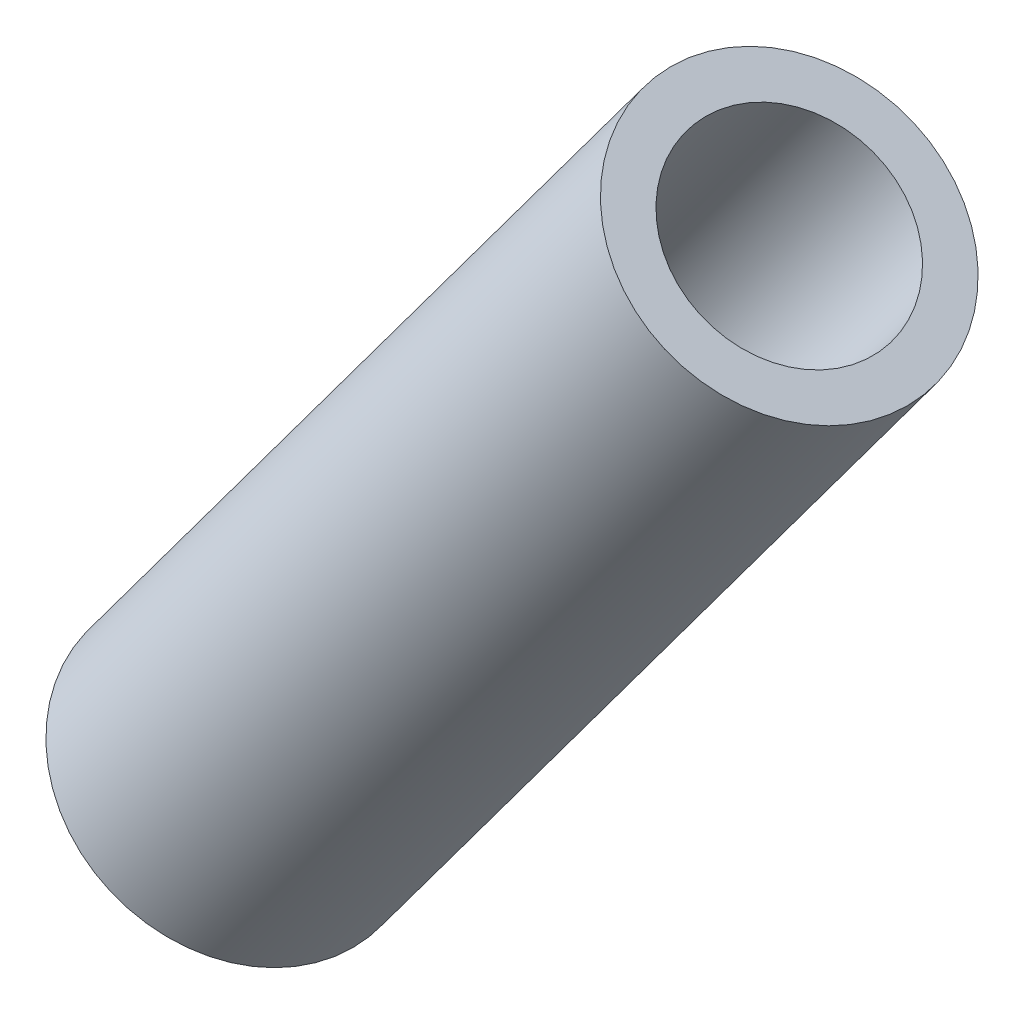
SolidWorks part; units mm, degrees
material "Silicon Rubber"
ref_plane "X-Y Datum" through (0, 0, 0) normal (0, 0, 1) x (1, 0, 0)
ref_plane "X-Z Datum" through (0, 0, 0) normal (0, 1, 0) x (1, 0, 0)
ref_plane "Y-Z Datum" through (0, 0, 0) normal (1, 0, 0) x (0, 0, -1)
sketch3d "3DSketch1"
  line L0 (-20.5114, -27.616, 0) -> (30.2901, 40.7817, 0)
  circle A0 centre (-20.5114, -27.616, 0) radius 10 construction
  circle A1 centre (-20.5114, -27.616, 0) radius 10 construction
  circle A2 centre (30.2901, 40.7817, 0) radius 9.5 construction
  circle A3 centre (30.2901, 40.7817, 0) radius 9.5 construction
  point P5 (-14.5488, -19.5881, 0)
  point P7 (-14.5488, -19.5881, 0)
  point P8 (0, 0, 0)
  point P11 (35.9546, 48.4082, 0)
  point P12 (35.9546, 48.4082, 0)
  point P13 (0, 0, 0)
  point P14 (0, 0, 0)
sweep "Sweep1" add path "3DSketch1" circular profile diameter 26.9875 parameters "D3"=26.9875
sweep "Cut-Sweep1" cut path "3DSketch1<2>" circular profile diameter 19.05 parameters "D3"=19.05
sketch3d "3DSketch1<2>" same geometry as "3DSketch1"
sketch3d "3DSketch2"
  line L0 (-20.5114, -27.616, 0) -> (30.2901, 40.7817, 0) construction
  circle A1 centre (4.8894, 6.5829, 0) radius 9.525 construction
  circle A4 centre (30.2901, 40.7817, 0) radius 9.525 construction
  point P4 (-0.79, -1.0637, 0)
  point P8 (24.6107, 33.1351, 0)
